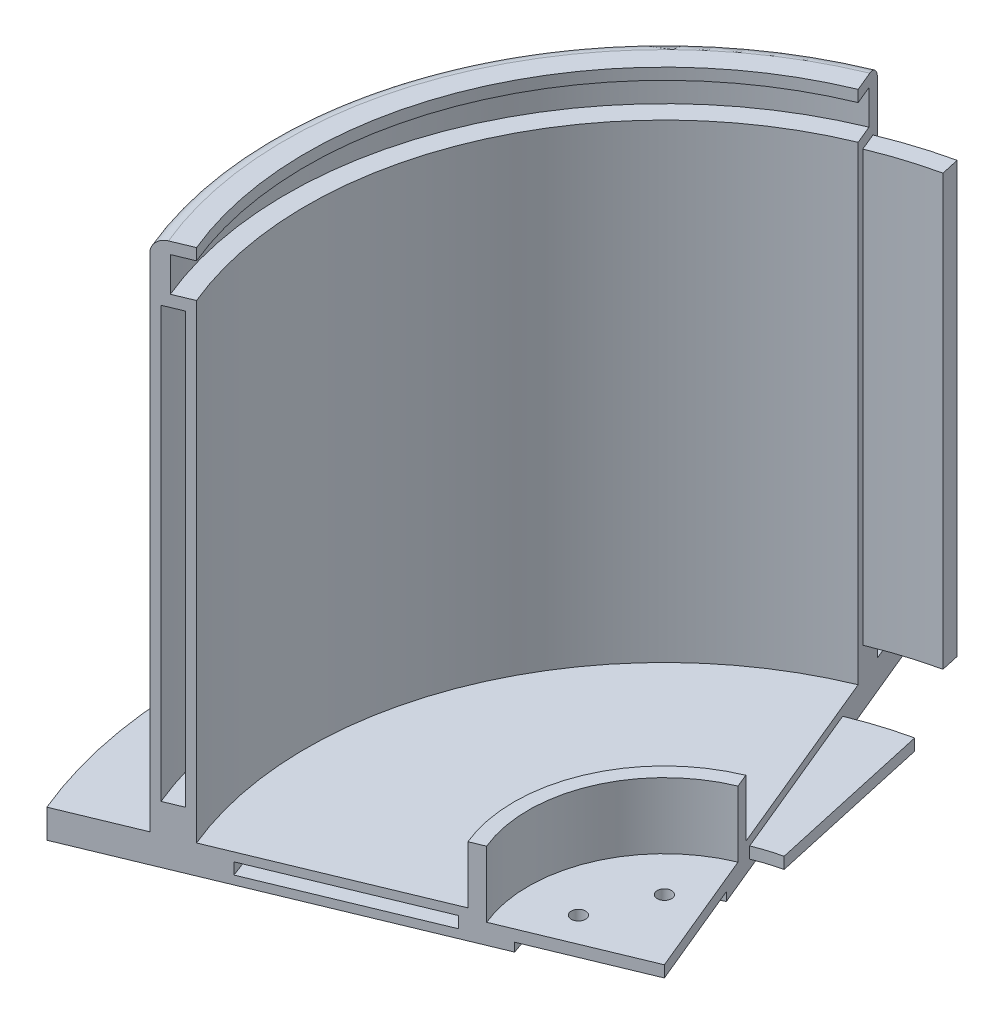
SolidWorks part; units mm, degrees
ref_plane "Front Plane" through (0, 0, 0) normal (0, 0, 1) x (1, 0, 0)
ref_plane "Top Plane" through (0, 0, 0) normal (0, 1, 0) x (1, 0, 0)
ref_plane "Right Plane" through (0, 0, 0) normal (1, 0, 0) x (0, 0, -1)
sketch "Sketch1" plane through (0, 0, 0) normal (0, 1, 0) x (1, 0, 0)
  circle A6 centre (0, 0) radius 125
  circle A7 centre (0, 0) radius 137.5
  dimension "D1" = 250
  dimension "D2" = 275
extrude "Boss-Extrude1" add sketch "Sketch1" along normal blind 180
sketch "Sketch2" plane through (0, 0, 0) normal (0, -1, 0) x (1, 0, 0)
  circle A0 centre (0, 0) radius 165
  circle A1 centre (0, 150) radius 2.5
  circle A2 centre (0, 30) radius 2.5
  circle A3 centre (106.066, 106.066) radius 2.5
  circle A4 centre (150, 0) radius 2.5
  circle A5 centre (106.066, -106.066) radius 2.5
  circle A6 centre (0, -150) radius 2.5
  circle A7 centre (-106.066, -106.066) radius 2.5
  circle A8 centre (-150, 0) radius 2.5
  circle A9 centre (-106.066, 106.066) radius 2.5
  circle A10 centre (21.2132, 21.2132) radius 2.5
  circle A11 centre (30, 0) radius 2.5
  circle A12 centre (21.2132, -21.2132) radius 2.5
  circle A13 centre (0, -30) radius 2.5
  circle A14 centre (-21.2132, -21.2132) radius 2.5
  circle A15 centre (-30, 0) radius 2.5
  circle A16 centre (-21.2132, 21.2132) radius 2.5
  point P24 (0, 0)
  point P39 (0, 0)
  dimension "D1" = 330
  dimension "D3" = 5
  dimension "D4" = 8
  dimension "D5" = 5
  dimension "D2" = 150
  dimension "D6" = 30
  dimension "D7" = 8
extrude "Boss-Extrude2" add sketch "Sketch2" along normal blind 10
sketch "Sketch3" plane through (0, 0, 0) normal (0, 1, 0) x (1, 0, 0)
  circle A0 centre (0, 0) radius 47.5
  circle A1 centre (0, 0) radius 52.5
  dimension "D1" = 95
  dimension "D2" = 105
extrude "Boss-Extrude3" add sketch "Sketch3" along normal blind 20
sketch "Sketch4" plane through (0, 0, 0) normal (1, 0, 0) x (0, 0, -1)
  line L0 (137.5, 180) -> (-137.5, 180) construction
  line L1 (-28, 160) -> (28, 160)
  line L2 (-28, 160) -> (-28, 64)
  line L3 (-28, 64) -> (28, 64)
  line L4 (28, 160) -> (28, 64)
  line L5 (-28, 160) -> (28, 64) construction
  line L6 (-28, 64) -> (28, 160) construction
  point P0 (0, 112)
  dimension "D1" = 56
  dimension "D2" = 96
  dimension "D3" = 20
extrude "Cut-Extrude4" cut sketch "Sketch4" along normal blind 150
sketch "Sketch5" plane through (0, 0, 28) normal (0, 0, -1) x (-1, 0, 0)
  line L1 (-149.8236, 140) -> (-93.8236, 140)
  line L2 (-149.8236, 140) -> (-149.8236, 130)
  line L3 (-149.8236, 130) -> (-93.8236, 130)
  line L4 (-93.8236, 140) -> (-93.8236, 130)
  line L5 (-149.8236, 140) -> (-93.8236, 130) construction
  line L6 (-149.8236, 130) -> (-93.8236, 140) construction
  line L7 (-137.5, 160) -> (-134.6189, 160) construction
  line L8 (-121.8236, 160) -> (-121.8236, 64) construction
  point P0 (-121.8236, 135)
  dimension "D1" = 10
  dimension "D2" = 25
  dimension "D3" = 56
extrude "Boss-Extrude4" add sketch "Sketch5" along normal up to surface (56 mm away) up to face at (128.2213, 112, -28)
sketch "Sketch6" plane through (0, 64, 0) normal (0, 1, 0) x (1, 0, 0)
  line L1 (93.8236, 28) -> (149.8236, 28)
  line L2 (93.8236, 28) -> (93.8236, -28)
  line L3 (93.8236, -28) -> (149.8236, -28)
  line L4 (149.8236, 28) -> (149.8236, -28)
extrude "Boss-Extrude5" add sketch "Sketch6" against normal blind 10
sketch "Sketch7" plane through (0, 140, 0) normal (0, 1, 0) x (1, 0, 0)
  line L1 (98.2736, 23.55) -> (145.3736, 23.55) construction
  line L2 (98.2736, 23.55) -> (98.2736, -23.55) construction
  line L3 (98.2736, -23.55) -> (145.3736, -23.55) construction
  line L4 (145.3736, 23.55) -> (145.3736, -23.55) construction
  line L5 (98.2736, 23.55) -> (145.3736, -23.55) construction
  line L6 (98.2736, -23.55) -> (145.3736, 23.55) construction
  circle A0 centre (98.2736, 23.55) radius 2.5
  circle A1 centre (145.3736, 23.55) radius 2.5
  circle A2 centre (98.2736, -23.55) radius 2.5
  circle A3 centre (145.3736, -23.55) radius 2.5
  circle A4 centre (121.8236, 0) radius 12.5
  point P0 (121.8236, 0)
  dimension "D3" = 25
  dimension "D4" = 5
  dimension "D1" = 47.1
  dimension "D2" = 47.1
extrude "Cut-Extrude5" cut sketch "Sketch7" against normal blind 10
sketch "Sketch8" plane through (149.8236, 0, 0) normal (1, 0, 0) x (0, 0, -1)
  line L1 (-28, 140) -> (28, 140)
  line L2 (-28, 140) -> (-28, 54)
  line L3 (-28, 54) -> (28, 54)
  line L4 (28, 140) -> (28, 54)
extrude "Boss-Extrude6" add sketch "Sketch8" along normal blind 5
fillet "Fillet1" radius 10 2 edges at (154.8236, 97, -28) (154.8236, 97, 28)
fillet "Fillet2" radius 5 4 edges at (93.8236, 59, -28) (93.8236, 59, 28) (93.8236, 135, 28) (93.8236, 135, -28)
sketch "Sketch9" plane through (0, 140, 0) normal (0, 1, 0) x (1, 0, 0)
  line L0 (93.8236, 23) -> (93.8236, -23) construction
  line L1 (77.9583, 3) -> (109.689, 3)
  line L2 (77.9583, 3) -> (77.9583, -3)
  line L3 (77.9583, -3) -> (109.689, -3)
  line L4 (109.689, 3) -> (109.689, -3)
  line L5 (77.9583, 3) -> (109.689, -3) construction
  line L6 (77.9583, -3) -> (109.689, 3) construction
  circle A0 centre (121.8236, 0) radius 12.5 construction
  point P0 (93.8236, 0)
  dimension "D1" = 6
extrude "Cut-Extrude6" cut sketch "Sketch9" against normal blind 10
fillet "Fillet3" radius 5 1 edges at (0, 180, 137.5)
sketch "Sketch10" plane through (0, 0, 0) normal (0, 1, 0) x (1, 0, 0)
  circle A0 centre (0, 0) radius 47.5
  dimension "D1" = 95
extrude "Cut-Extrude7" cut sketch "Sketch10" against normal blind 3
sketch "Sketch11" plane through (0, 0, 0) normal (0, 1, 0) x (1, 0, 0)
  circle A0 centre (0, 150) radius 5
  circle A1 centre (106.066, 106.066) radius 5
  circle A2 centre (150, 0) radius 5
  circle A3 centre (106.066, -106.066) radius 5
  circle A4 centre (0, -150) radius 5
  circle A5 centre (-106.066, -106.066) radius 5
  circle A6 centre (-150, 0) radius 5
  circle A7 centre (-106.066, 106.066) radius 5
  point P19 (0, 0)
  dimension "D1" = 10
  dimension "D2" = 8
extrude "Cut-Extrude8" cut sketch "Sketch11" against normal blind 5
sketch "Sketch13" plane through (0, 0, 0) normal (0, 0, 1) x (1, 0, 0)
  line L1 (-132, 176) -> (-118, 176)
  line L2 (-132, 176) -> (-132, 164)
  line L3 (-132, 164) -> (-118, 164)
  line L4 (-118, 176) -> (-118, 164)
  line L5 (-132, 176) -> (-118, 164) construction
  line L6 (-132, 164) -> (-118, 176) construction
  line L7 (0, 0) -> (0, 216.6626) construction
  line L8 (132.5, 180) -> (-132.5, 180) construction
  point P0 (-125, 170)
  dimension "D1" = 12
  dimension "D2" = 14
  dimension "D3" = 125
  dimension "D4" = 4
revolve "Cut-Revolve1" cut sketch "Sketch13" angle 360 about L7
sketch "Sketch14" plane through (0, 180, 0) normal (0, 1, 0) x (1, 0, 0)
  line L0 (0, 0) -> (152.4401, 63.1428)
  line L1 (0, 0) -> (-63.1428, 152.4401)
  line L2 (0, 0) -> (-152.4401, -63.1428)
  line L3 (0, 0) -> (63.1428, -152.4401)
  line L4 (0, 0) -> (165, 0) construction
  circle A0 centre (0, 0) radius 165 construction
  circle A1 centre (0, 0) radius 165
  circle M4 centre (0, 0) radius 132.5
  circle M5 centre (0, 0) radius 125
  dimension "D3" = 330
  dimension "D1" = 22.5
  dimension "D2" = 90
extrude "Cut-Extrude9" cut sketch "Sketch14" against normal through all contours L1 L0 M5 | L1 L0 M5 M4 | L0 A1 L1 M4 | L4 A1 L0 M4 | L0 L4 M5 | L4 L0 M5 M4 | L4 L3 A1 M4 | L4 L3 M5 M4 | L4 L3 M5 | L2 A1 L3 M4 | L3 L2 M5 M4 | L3 L2 M5 region at (28.7113, 180, -69.3153) region at (-28.7113, 180, 69.3153) region at (65.3511, 180, 43.6662) region at (81.2079, 180, -16.1533) region at (48.5729, 180, -117.2654) region at (125.5018, 180, -24.9639) region at (-48.5729, 180, 117.2654) region at (105.1713, 180, 70.2732) region at (51.4536, 180, -124.22) region at (145.5328, 180, -28.9483) region at (-51.4536, 180, 124.22) region at (117.1158, 180, 78.2543)
sketch "Sketch15" plane through (0, 0, 0) normal (0.9239, 0, -0.3827) x (-0.3827, 0, -0.9239)
  line L1 (134.5, 160) -> (128, 160)
  line L2 (134.5, 160) -> (134.5, 10)
  line L3 (134.5, 10) -> (128, 10)
  line L4 (128, 160) -> (128, 10)
  line L5 (134.5, 160) -> (128, 10) construction
  line L6 (134.5, 10) -> (128, 160) construction
  line L10 (55, -7) -> (115, -7)
  line L11 (55, -7) -> (55, -3)
  line L12 (55, -3) -> (115, -3)
  line L13 (115, -7) -> (115, -3)
  line L14 (55, -7) -> (115, -3) construction
  line L15 (55, -3) -> (115, -7) construction
  line L17 (125, 0) -> (0, 0) construction
  line L18 (0, 0) -> (0, 180) construction
  line L19 (0, -10) -> (165, -10) construction
  line L20 (125, 0) -> (125, 164) construction
  line L21 (137.5, 0) -> (137.5, 175) construction
  point P0 (131.25, 85)
  point P11 (85, -5)
  dimension "D1" = 55
  dimension "D2" = 150
  dimension "D3" = 3
  dimension "D4" = 3
  dimension "D5" = 3
  dimension "D6" = 60
  dimension "D7" = 3
  dimension "D8" = 95
revolve "Revolve1" add sketch "Sketch15" angle 10 about L18 reverse direction yes
sketch "Sketch16" plane through (0, 0, 0) normal (0.3827, 0, 0.9239) x (0.9239, 0, -0.3827)
  line L0 (0, 0) -> (0, 54.6917) construction
  line L1 (-134.5, 160) -> (-128, 160)
  line L2 (-134.5, 160) -> (-134.5, 10)
  line L3 (-134.5, 10) -> (-128, 10)
  line L4 (-128, 160) -> (-128, 10)
  line L5 (-134.5, 160) -> (-128, 10) construction
  line L6 (-134.5, 10) -> (-128, 160) construction
  line L7 (-115, -7) -> (-55, -7)
  line L8 (-115, -7) -> (-115, -3)
  line L9 (-115, -3) -> (-55, -3)
  line L10 (-55, -7) -> (-55, -3)
  line L11 (-115, -7) -> (-55, -3) construction
  line L12 (-115, -3) -> (-55, -7) construction
  line L13 (0, 0) -> (0, 164) construction
  line L18 (0, -10) -> (-165, -10) construction
  line L19 (-137.5, 0) -> (-137.5, 175) construction
  line L20 (-125, 0) -> (-125, 164) construction
  line L21 (0, 0) -> (-125, 0) construction
  point P0 (-131.25, 85)
  point P5 (-85, -5)
  dimension "D1" = 95
  dimension "D2" = 3
  dimension "D3" = 3
  dimension "D4" = 150
  dimension "D5" = 3
  dimension "D6" = 3
  dimension "D7" = 55
  dimension "D8" = 60
revolve "Cut-Revolve2" cut sketch "Sketch16" angle 10 about L0 reverse direction yes
sketch "Sketch17" plane through (0, -10, 0) normal (0, -1, 0) x (1, 0, 0)
  circle A0 centre (0, 0) radius 40
  dimension "D1" = 80
extrude "Cut-Extrude10" cut sketch "Sketch17" against normal blind 3
ref_plane "Plane1" through (-81.6602, 0, -33.8248) normal (0.9239, 0, 0.3827) x (0.3827, 0, -0.9239)
